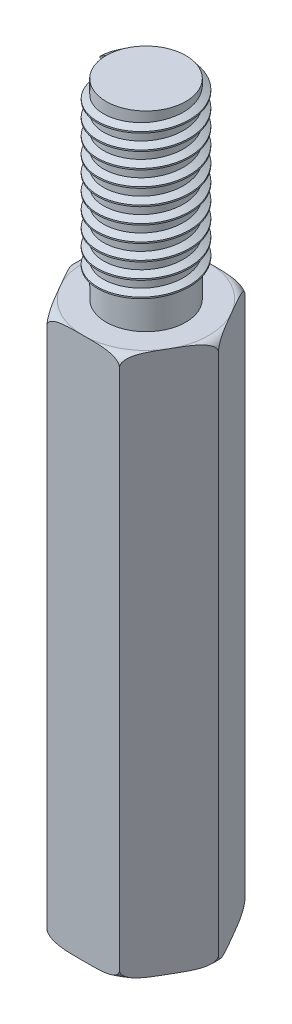
SolidWorks part; units mm, degrees
ref_plane "Front Plane" through (0, 0, 0) normal (0, 0, 1) x (1, 0, 0)
ref_plane "Top Plane" through (0, 0, 0) normal (0, 1, 0) x (1, 0, 0)
ref_plane "Right Plane" through (0, 0, 0) normal (1, 0, 0) x (0, 0, -1)
sketch "Sketch1" plane through (0, 0, 0) normal (0, 1, 0) x (1, 0, 0)
  line L1 (1.1374, 1.97) -> (-1.1374, 1.97)
  line L2 (-1.1374, 1.97) -> (-2.2748, 0)
  line L3 (-2.2748, 0) -> (-1.1374, -1.97)
  line L4 (-1.1374, -1.97) -> (1.1374, -1.97)
  line L5 (1.1374, -1.97) -> (2.2748, 0)
  line L6 (2.2748, 0) -> (1.1374, 1.97)
  circle A0 centre (0, 0) radius 1.97 construction
  dimension "D1" = 3.94
extrude "Boss-Extrude1" add sketch "Sketch1" along normal mid plane 17
sketch "Sketch2" plane through (0, 8.5, 0) normal (0, 1, 0) x (1, 0, 0)
  circle A0 centre (0, 0) radius 1.25
  dimension "D1" = 2.5
extrude "Boss-Extrude2" add sketch "Sketch2" along normal blind 6
sketch "Sketch3" plane through (0, -8.5, 0) normal (0, -1, 0) x (1, 0, 0)
  circle A0 centre (0, 0) radius 1.25
  circle A1 centre (0, 0) radius 1.25 construction
extrude "Cut-Extrude1" cut sketch "Sketch3" against normal blind 7
thread "Thread1" pitch 0.35 method extrude profile "Thread Profile1" start angle 0, offset 0, length 5, pitch 0.5, diameter 2.5
ref_plane "Plane1" through (-1.25, 14.5, 0) normal (0, 0, 1) x (-1, 0, 0)
sketch "Thread Profile1" plane through (-1.25, 14.5, 0) normal (0, 0, 1) x (-1, 0, 0)
  line L0 (0, 0) -> (0, 0.35) construction
  line L1 (0, 0) -> (0.1894, 0.1094)
  line L2 (0.1894, 0.1094) -> (0.1894, 0.1531)
  line L3 (0.1894, 0.1531) -> (0, 0.2625)
  line L4 (0.1894, 0.1312) -> (0, 0.1312) construction
  line L11 (0, 0) -> (0, 0.2625)
  point P2 (0, 0)
  dimension "Pitch" = 0.35
  dimension "Profile_Angle" = 60
  dimension "Profile_Land" = 0.0437
  dimension "Profile_Height" = 0.1894
thread "Thread2" pitch 0.35 method cut profile "Thread Profile2" start angle 0, offset 0, length 7, pitch 0.5, diameter 2.5
ref_plane "Plane2" through (1.25, -8.5, 0) normal (0, 0, 1) x (1, 0, 0)
sketch "Thread Profile2" plane through (1.25, -8.5, 0) normal (0, 0, 1) x (1, 0, 0)
  line L0 (0, 0) -> (0, 0.35) construction
  line L1 (0, 0) -> (0.1894, 0.1094)
  line L2 (0.1894, 0.1094) -> (0.1894, 0.1531)
  line L3 (0.1894, 0.1531) -> (0, 0.2625)
  line L4 (0.1894, 0.1312) -> (0, 0.1312) construction
  line L11 (0, 0) -> (0, 0.2625)
  point P2 (0, 0)
  dimension "Pitch" = 0.35
  dimension "Profile_Angle" = 60
  dimension "Profile_Land" = 0.0437
  dimension "Profile_Height" = 0.1894
sketch "Sketch4" plane through (0, 0, 0) normal (0, 0, 1) x (1, 0, 0)
  line L0 (0, 8.5) -> (0, -8.5) construction
  line L2 (-1.25, -8.5) -> (1.25, -8.5) construction
  line L3 (0, -8.5) -> (1.97, -8.5) construction
  line L4 (0, 8.5) -> (1.97, 8.5) construction
  line L5 (2.2748, 8.5) -> (2.2748, -8.5) construction
  line L6 (1.97, 8.5) -> (2.2748, 8.5)
  line L7 (2.2748, 8.5) -> (2.2748, 8.1952)
  line L8 (2.2748, -8.1952) -> (2.2748, -8.5)
  line L9 (2.2748, -8.5) -> (1.97, -8.5)
  arc A0 (1.97, -8.5) -> (2.2748, -8.1952) centre (1.97, -8.1952) ccw
  arc A1 (2.2748, 8.1952) -> (1.97, 8.5) centre (1.97, 8.1952) ccw
  point P13 (0, 0)
  dimension "D1" = 1.97
revolve "Cut-Revolve1" cut sketch "Sketch4" angle 360 about L0
